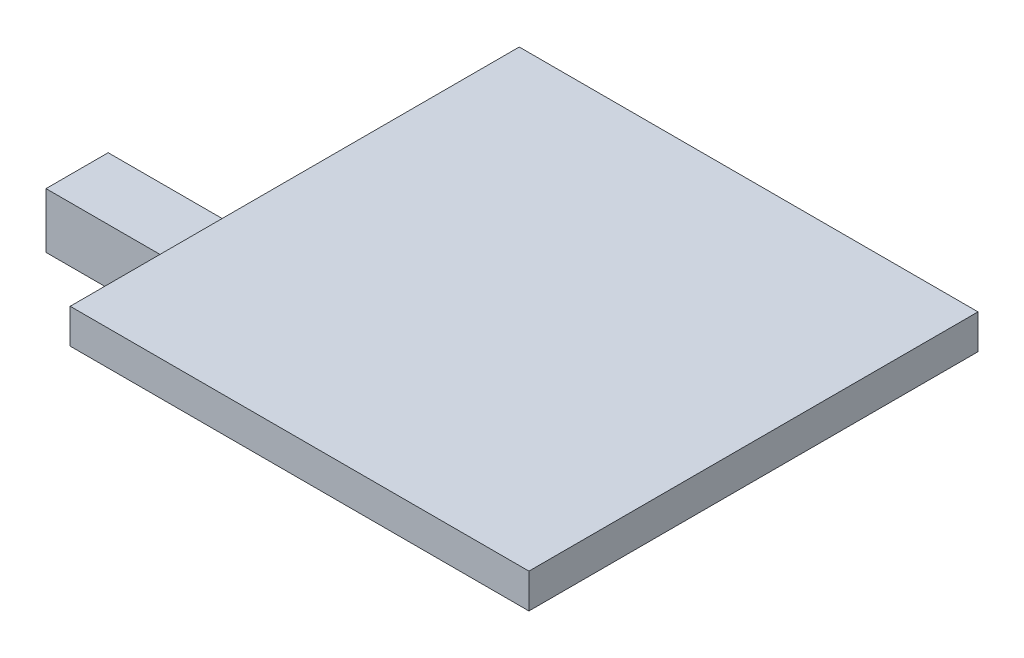
SolidWorks part; units mm, degrees
ref_plane "Front Plane" through (0, 0, 0) normal (0, 0, 1) x (1, 0, 0)
ref_plane "Top Plane" through (0, 0, 0) normal (0, 1, 0) x (1, 0, 0)
ref_plane "Right Plane" through (0, 0, 0) normal (1, 0, 0) x (0, 0, -1)
sketch "Sketch1" plane through (0, 0, 0) normal (0, 0, 1) x (1, 0, 0)
  line L0 (-65.5935, -8.0113) -> (-65.5935, -18.0113)
  line L1 (-65.5935, -18.0113) -> (67.2065, -18.0113)
  line L2 (67.2065, -18.0113) -> (67.2065, -8.0113)
  line L3 (67.2065, -8.0113) -> (-65.5935, -8.0113)
  dimension "D1" = 132.8
  dimension "D2" = 10
extrude "Boss-Extrude1" add sketch "Sketch1" along normal blind 130
sketch "Sketch3" plane through (0, -18.0113, 0) normal (0, -1, 0) x (1, 0, 0)
  line L0 (-65.5935, 85) -> (-37.6211, 85) construction
  line L1 (-65.5935, 130) -> (-65.5935, 0) construction
  line L2 (-65.5935, 76) -> (-55.5935, 76)
  line L3 (-55.5935, 76) -> (-55.5935, 94)
  line L4 (-55.5935, 94) -> (-65.5935, 94)
  line L5 (-65.5935, 94) -> (-65.5935, 76)
  line L6 (-65.5935, 65) -> (-69.4095, 65) construction
  point P4 (-65.5935, 65)
  dimension "D1" = 20
  dimension "D2" = 9
  dimension "D3" = 9
  dimension "D4" = 10
extrude "Boss-Extrude2" add sketch "Sketch3" along normal blind 16
sketch "Sketch4" plane through (-65.5935, 0, 0) normal (-1, 0, 0) x (0, 0, 1)
  line L0 (76, -18.0113) -> (94, -18.0113)
  line L1 (94, -18.0113) -> (94, -34.0113)
  line L2 (94, -34.0113) -> (76, -34.0113)
  line L3 (76, -34.0113) -> (76, -18.0113)
extrude "Boss-Extrude3" add sketch "Sketch4" along normal blind 43
sketch "Sketch5" plane through (0, 0, 94) normal (0, 0, 1) x (1, 0, 0)
  line L5 (-65.5935, -18.0113) -> (-57.5935, -18.0113)
  line L6 (-65.5935, -18.0113) -> (67.2065, -18.0113) construction
  line L7 (-57.5935, -18.0113) -> (-57.5935, -34.0113)
  line L8 (-55.5935, -34.0113) -> (-108.5935, -34.0113) construction
  line L9 (-57.5935, -34.0113) -> (-65.5935, -34.0113)
  line L10 (-65.5935, -34.0113) -> (-65.5935, -18.0113)
  dimension "D1" = 8
extrude "Boss-Extrude4" add sketch "Sketch5" along normal blind 10
sketch "Sketch6" plane through (0, 0, 76) normal (0, 0, -1) x (-1, 0, 0)
  line L0 (65.5935, -18.0113) -> (57.5935, -18.0113)
  line L1 (65.5935, -18.0113) -> (-67.2065, -18.0113) construction
  line L2 (57.5935, -18.0113) -> (57.5935, -34.0113)
  line L3 (108.5935, -34.0113) -> (55.5935, -34.0113) construction
  line L4 (57.5935, -34.0113) -> (65.5935, -34.0113)
  line L5 (65.5935, -34.0113) -> (65.5935, -18.0113)
  dimension "D1" = 8
extrude "Boss-Extrude5" add sketch "Sketch6" along normal blind 10
sketch "Sketch7" plane through (0, 0, 76) normal (0, 0, -1) x (-1, 0, 0)
  line L0 (57.5935, -18.0113) -> (55.5935, -18.0113)
  line L1 (55.5935, -18.0113) -> (55.5935, -34.0113)
  line L2 (55.5935, -34.0113) -> (57.5935, -34.0113)
  line L3 (57.5935, -34.0113) -> (57.5935, -18.0113)
extrude "Cut-Extrude1" cut sketch "Sketch7" against normal blind 20
